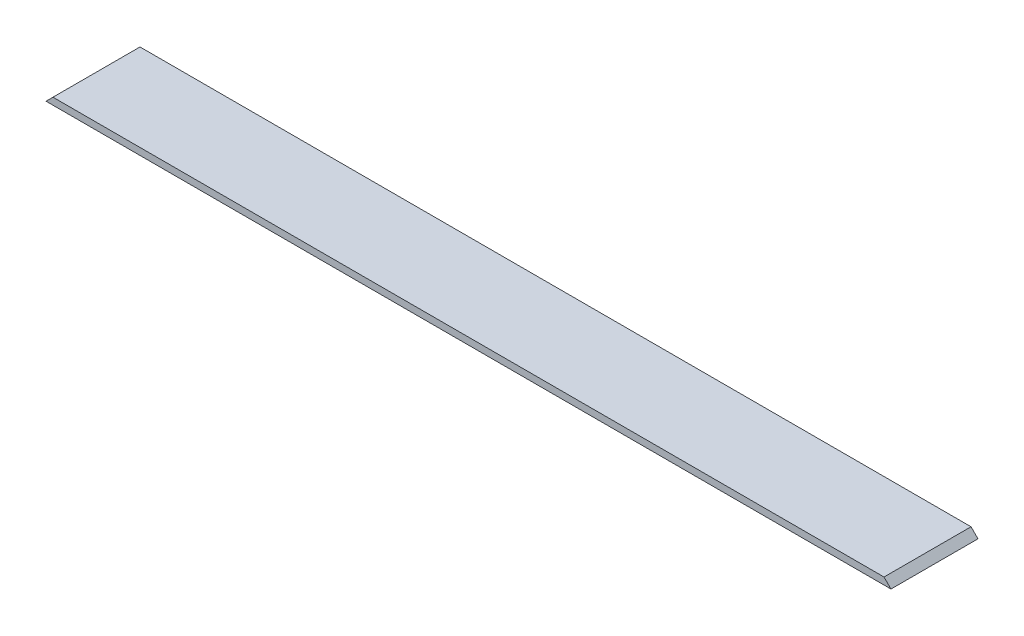
SolidWorks part; units mm, degrees
material "Pine"
ref_plane "Front Plane" through (0, 0, 0) normal (0, 0, 1) x (1, 0, 0)
ref_plane "Top Plane" through (0, 0, 0) normal (0, 1, 0) x (1, 0, 0)
ref_plane "Right Plane" through (0, 0, 0) normal (1, 0, 0) x (0, 0, -1)
sketch "Sketch1" plane through (0, 0, 0) normal (0, 0, 1) x (1, 0, 0)
  line L0 (-279.7605, 0) -> (336.8245, 0)
  line L1 (336.8245, 0) -> (331.7445, 5.08)
  line L2 (331.7445, 5.08) -> (-274.6805, 5.08)
  line L3 (-274.6805, 5.08) -> (-279.7605, 0)
  dimension "D1" = 606.425
  dimension "D2" = 45
  dimension "D3" = 45
  dimension "D4" = 5.08
extrude "Boss-Extrude1" add sketch "Sketch1" along normal blind 63.5
